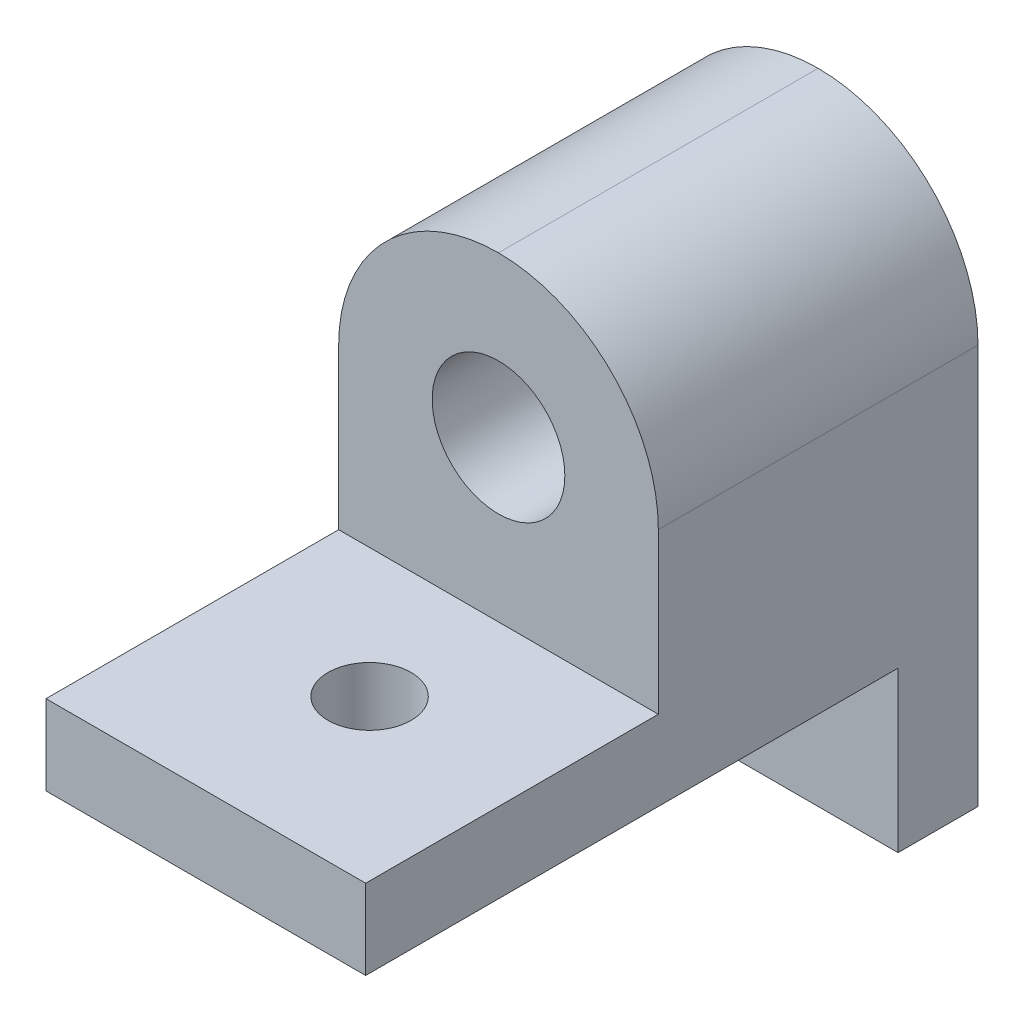
SolidWorks part; units mm, degrees
ref_plane "前视基准面" through (0, 0, 0) normal (0, 0, 1) x (1, 0, 0)
ref_plane "上视基准面" through (0, 0, 0) normal (0, 1, 0) x (1, 0, 0)
ref_plane "右视基准面" through (0, 0, 0) normal (1, 0, 0) x (0, 0, -1)
sketch "草图1" plane through (0, 0, 0) normal (0, 1, 0) x (1, 0, 0)
  line L1 (-7.3659, -8.1541) -> (12.6341, -8.1541)
  line L2 (-7.3659, -8.1541) -> (-7.3659, -48.1541)
  line L3 (-7.3659, -48.1541) -> (12.6341, -48.1541)
  line L4 (12.6341, -8.1541) -> (12.6341, -48.1541)
  dimension "D1" = 20
  dimension "D2" = 40
extrude "凸台-拉伸1" add sketch "草图1" along normal blind 5
sketch "草图2" plane through (0, 5, 0) normal (0, 1, 0) x (1, 0, 0)
  line L0 (-7.3659, -8.1541) -> (-7.3659, -48.1541) construction
  line L1 (-7.3659, -18.1541) -> (12.6341, -18.1541)
  line L2 (-7.3659, -18.1541) -> (-7.3659, -38.1541)
  line L3 (-7.3659, -38.1541) -> (12.6341, -38.1541)
  line L4 (12.6341, -18.1541) -> (12.6341, -38.1541)
  line L5 (12.6341, -48.1541) -> (12.6341, -8.1541) construction
  line L6 (12.6341, -8.1541) -> (-7.3659, -8.1541) construction
  line L7 (-7.3659, -48.1541) -> (12.6341, -48.1541) construction
  dimension "D1" = 10
  dimension "D2" = 10
extrude "凸台-拉伸2" add sketch "草图2" along normal blind 20
sketch "草图3" plane through (0, 0, 38.1541) normal (0, 0, 1) x (1, 0, 0)
  circle A0 centre (2.6341, 15) radius 4.15
  dimension "D1" = 8.3
extrude "切除-拉伸1" cut sketch "草图3" against normal through all
fillet "圆角1" radius 10 2 edges at (12.6341, 25, 28.1541) (-7.3659, 25, 28.1541)
sketch "草图6" plane through (0, 5, 0) normal (0, 1, 0) x (1, 0, 0)
  line L1 (-7.3659, -18.1541) -> (12.6341, -18.1541)
  line L2 (-7.3659, -18.1541) -> (-7.3659, 7.6374)
  line L3 (-7.3659, 7.6374) -> (12.6341, 7.6374)
  line L4 (12.6341, -18.1541) -> (12.6341, 7.6374)
extrude "切除-拉伸3" cut sketch "草图6" against normal through all
sketch "草图7" plane through (0, 0, 0) normal (0, -1, 0) x (1, 0, 0)
  line L0 (12.6341, 48.1541) -> (12.6341, 18.1541) construction
  line L5 (-7.3659, 18.1541) -> (12.6341, 18.1541)
  line L6 (-7.3659, 18.1541) -> (-7.3659, 23.1541)
  line L7 (-7.3659, 23.1541) -> (12.6341, 23.1541)
  line L8 (12.6341, 18.1541) -> (12.6341, 23.1541)
  dimension "D1" = 5
extrude "凸台-拉伸5" add sketch "草图7" along normal blind 10
sketch "草图8" plane through (0, 0, 48.1541) normal (0, 0, 1) x (1, 0, 0)
  line L4 (-7.3659, 0) -> (12.6341, 0)
  line L5 (12.6341, 0) -> (12.6341, 5)
  line L6 (12.6341, 5) -> (-7.3659, 5)
  line L7 (-7.3659, 5) -> (-7.3659, 0)
  line L8 (-7.3659, 0) -> (12.6341, 0)
  line L9 (12.6341, 0) -> (12.6341, 5)
  line L10 (12.6341, 5) -> (-7.3659, 5)
  line L11 (-7.3659, 5) -> (-7.3659, 0)
  dimension "D1" = 0
extrude "凸台-拉伸6" add sketch "草图8" along normal blind 10
sketch "草图10" plane through (0, 0, 23.1541) normal (0, 0, 1) x (1, 0, 0)
  line L0 (12.6341, -10) -> (-7.3659, -10) construction
  circle A0 centre (2.6341, -5) radius 1.6
  dimension "D1" = 3.2
  dimension "D2" = 5
extrude "切除-拉伸5" cut sketch "草图10" against normal through all
sketch "草图11" plane through (0, 0, 58.1541) normal (0, 0, 1) x (1, 0, 0)
  line L4 (-7.3659, 5) -> (-7.3659, 0)
  line L5 (-7.3659, 0) -> (12.6341, 0)
  line L6 (12.6341, 0) -> (12.6341, 5)
  line L7 (12.6341, 5) -> (-7.3659, 5)
  line L8 (-7.3659, 5) -> (-7.3659, 0)
  line L9 (-7.3659, 0) -> (12.6341, 0)
  line L10 (12.6341, 0) -> (12.6341, 5)
  line L11 (12.6341, 5) -> (-7.3659, 5)
  dimension "D1" = 0
extrude "凸台-拉伸7" add sketch "草图11" along normal blind 20
sketch "草图12" plane through (0, 5, 0) normal (0, 1, 0) x (1, 0, 0)
  circle A0 centre (2.6341, -46.2217) radius 2.6
  circle A1 centre (2.6341, -72.1102) radius 2.6
  dimension "D1" = 5.2
  dimension "D2" = 5.2
extrude "切除-拉伸7" cut sketch "草图12" against normal through all
sketch "草图13" plane through (0, 5, 0) normal (0, 1, 0) x (1, 0, 0)
  line L0 (12.6341, -78.1541) -> (12.6341, -38.1541) construction
  line L1 (-7.3659, -78.1541) -> (12.6341, -78.1541)
  line L2 (-7.3659, -78.1541) -> (-7.3659, -56.4651)
  line L3 (-7.3659, -56.4651) -> (12.6341, -56.4651)
  line L4 (12.6341, -78.1541) -> (12.6341, -56.4651)
extrude "切除-拉伸8" cut sketch "草图13" against normal through all
